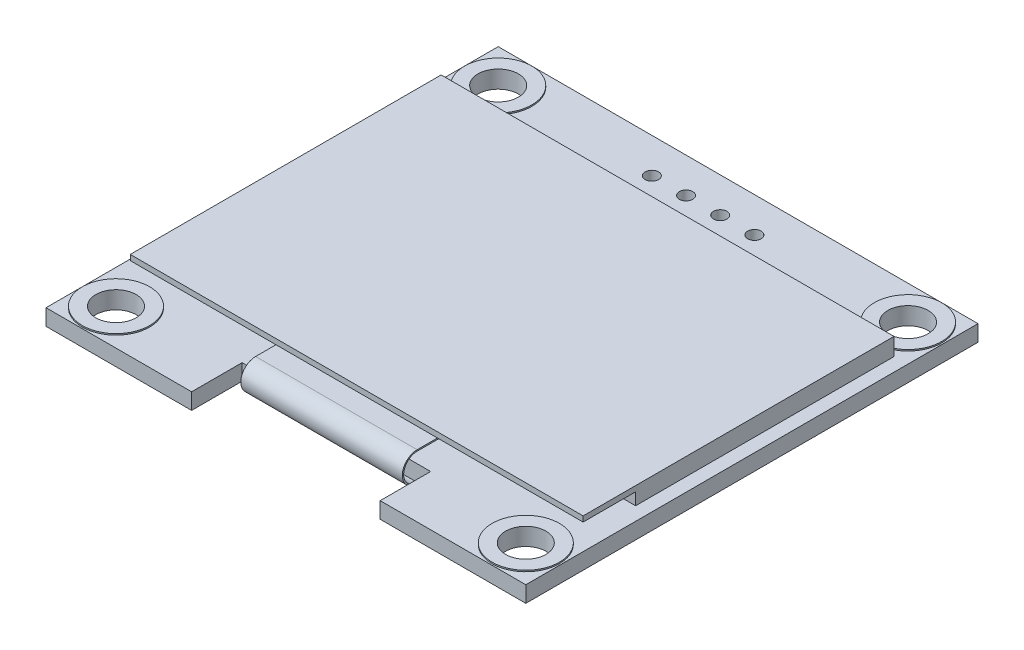
SolidWorks part; units mm, degrees
ref_plane "Alzado" through (0, 0, 0) normal (0, 0, 1) x (1, 0, 0)
ref_plane "Planta" through (0, 0, 0) normal (0, 1, 0) x (1, 0, 0)
ref_plane "Vista lateral" through (0, 0, 0) normal (1, 0, 0) x (0, 0, -1)
sketch "Croquis1" plane through (0, 0, 0) normal (0, 1, 0) x (1, 0, 0)
  line L0 (-7.005, 0) -> (7.005, 0)
  line L1 (-50, 0) -> (50, 0) construction
  line L2 (0, 29.85) -> (0, 0) construction
  line L3 (7.005, 0) -> (7.005, -3.75)
  line L4 (7.005, -3.75) -> (17.825, -3.75)
  line L5 (17.825, -3.75) -> (17.825, 29.85)
  line L6 (17.825, 29.85) -> (-17.825, 29.85)
  line L7 (-17.825, 29.85) -> (-17.825, -3.75)
  line L8 (-17.825, -3.75) -> (-7.005, -3.75)
  line L9 (-7.005, -3.75) -> (-7.005, 0)
  line L10 (-15.225, 27.25) -> (-15.225, -1.15) construction
  line L11 (-15.225, -1.15) -> (15.225, -1.15) construction
  line L12 (15.225, -1.15) -> (15.225, 27.25) construction
  line L13 (15.225, 27.25) -> (-15.225, 27.25) construction
  line L14 (-1.27, 26.75) -> (1.27, 26.75) construction
  circle A0 centre (-15.225, 27.25) radius 2.5
  circle A1 centre (15.225, 27.25) radius 2.5
  circle A2 centre (-15.225, -1.15) radius 2.5
  circle A3 centre (15.225, -1.15) radius 2.5
  circle A4 centre (-1.27, 27.25) radius 0.5
  circle A5 centre (-3.81, 27.25) radius 0.5
  circle A6 centre (1.27, 27.25) radius 0.5
  circle A7 centre (3.81, 27.25) radius 0.5
  point P6 (0, 0)
  point P32 (0, 26.75)
  dimension "D5" = 5
  dimension "D10" = 1
  dimension "D1" = 10.82
  dimension "D2" = 35.65
  dimension "D3" = 33.6
  dimension "D4" = 3.75
  dimension "D6" = 2.6
  dimension "D7" = 2.6
  dimension "D8" = 2.6
  dimension "D9" = 2.6
  dimension "D11" = 2.54
  dimension "D12" = 2.54
  dimension "D13" = 2.54
extrude "Saliente-Extruir1" add sketch "Croquis1" along normal blind 1.2 separate body
sketch "Croquis2" plane through (0, 1.2, 0) normal (0, 1, 0) x (1, 0, 0)
  circle A0 centre (-15.225, 27.25) radius 2.5
  circle A1 centre (-15.225, 27.25) radius 1.5
  circle A2 centre (15.225, 27.25) radius 2.5
  circle A3 centre (-15.225, -1.15) radius 2.5
  circle A4 centre (15.225, -1.15) radius 2.5
  circle A5 centre (15.225, 27.25) radius 1.5
  circle A6 centre (15.225, -1.15) radius 1.5
  circle A7 centre (-15.225, -1.15) radius 1.5
  dimension "D1" = 5
  dimension "D2" = 3
extrude "Saliente-Extruir2" add sketch "Croquis2" along direction (0, 1, 0) on the side against the normal up to surface (1.2 mm away) and the other way blind 0.1 separate body up to face at (0, 0, -5.5875)
sketch "Croquis3" plane through (0, 0, 0) normal (1, 0, 0) x (0, 0, -1)
  line L0 (24.61, 1.2) -> (24.61, 2.5)
  line L1 (-3.75, 1.2) -> (29.85, 1.2) construction
  line L2 (24.61, 2.5) -> (1.51, 2.5)
  line L3 (1.51, 2.5) -> (1.51, 2.1)
  line L4 (1.51, 2.1) -> (5.41, 2.1)
  line L5 (5.41, 2.1) -> (5.41, 1.2)
  line L6 (5.41, 1.2) -> (24.61, 1.2)
  line L7 (-3.75, 1.2) -> (-3.75, 0) construction
  dimension "D1" = 1.3
  dimension "D2" = 0.9
  dimension "D3" = 23.1
  dimension "D4" = 5.26
  dimension "D5" = 3.9
extrude "Saliente-Extruir3" add sketch "Croquis3" along normal blind 16.825 and the other way blind 16.825 separate body
sketch "Croquis4" plane through (0, 0, 0) normal (0, -1, 0) x (1, 0, 0)
  line L0 (11, -7) -> (-11, -7)
  line L1 (-11, -7) -> (-11, -4)
  line L2 (-11, -4) -> (-6, -2.5585)
  line L3 (-6, -2.5585) -> (-6, 0)
  line L4 (11, -7) -> (11, -4)
  line L5 (11, -4) -> (6, -2.5585)
  line L6 (6, -2.5585) -> (6, 0)
  line L7 (6, 0) -> (-6, 0)
  line L8 (0, -7) -> (0, 0) construction
  line L9 (-7.005, 0) -> (7.005, 0) construction
  point P11 (0, 0)
  dimension "D1" = 22
  dimension "D2" = 12
  dimension "D3" = 3
  dimension "D4" = 2.5585
  dimension "D5" = 7
extrude "Saliente-Extruir4" add sketch "Croquis4" along normal blind 0.1 separate body
sketch "Croquis5" plane through (0, 0, 0) normal (1, 0, 0) x (0, 0, -1)
  line L0 (1.51, 2.1) -> (3.0684, 2.1)
  line L1 (1.51, 2.1) -> (5.41, 2.1) construction
  line L2 (1.51, 2.1) -> (0, 2.1)
  line L3 (0, 50) -> (0, -50) construction
  line L4 (2.5585, -0.1) -> (0, -0.1) construction
  line L5 (1.51, 2) -> (3.0684, 2)
  line L6 (1.51, 2) -> (0, 2)
  line L7 (3.0684, 2.1) -> (3.0684, 2)
  line L8 (0, 0) -> (0, -0.1)
  arc A0 (0, 2.1) -> (0, -0.1) centre (0, 1) ccw
  arc A1 (0, 2) -> (0, 0) centre (0, 1) ccw
  dimension "D1" = 0.1
extrude "Saliente-Extruir5" add sketch "Croquis5" along normal up to vertex (6 mm away) and the other way up to vertex (6 mm away) up to point (6, -0.1, 0) other way up to point (-6, -0.1, 0)
sketch "Líneas de pliegue1" [suppressed] plane through (0, 0, 0) normal (0, 1, 0) x (1, 0, 0)
sketch "Cuadro delimitador1" [suppressed] plane through (0, 0, 0) normal (0, 1, 0) x (1, 0, 0)
